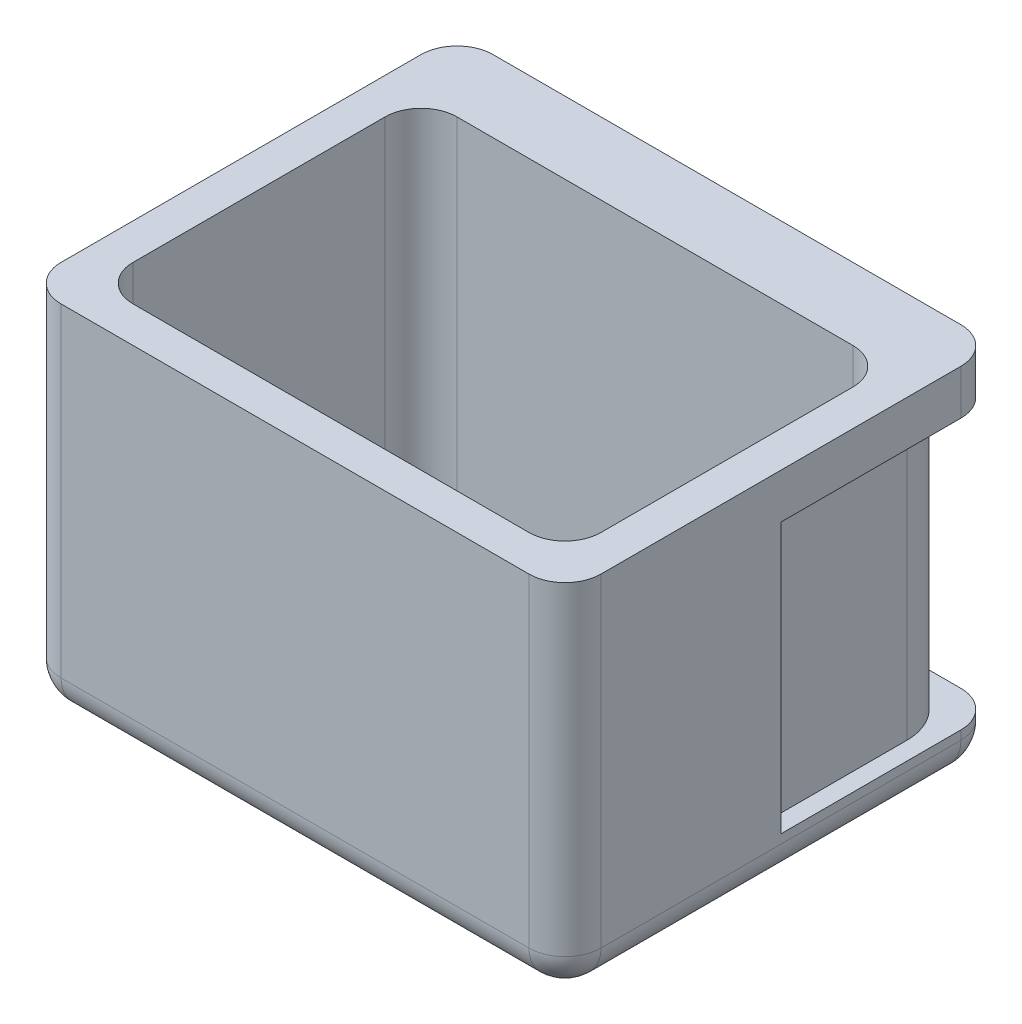
SolidWorks part; units mm, degrees
ref_plane "Front Plane" through (0, 0, 0) normal (0, 0, 1) x (1, 0, 0)
ref_plane "Top Plane" through (0, 0, 0) normal (0, 1, 0) x (1, 0, 0)
ref_plane "Right Plane" through (0, 0, 0) normal (1, 0, 0) x (0, 0, -1)
sketch "Sketch1" plane through (0, 0, 0) normal (0, 1, 0) x (1, 0, 0)
  line L1 (-75, -60) -> (75, -60)
  line L2 (-75, -60) -> (-75, 60)
  line L3 (-75, 60) -> (75, 60)
  line L4 (75, -60) -> (75, 60)
  line L5 (-75, -60) -> (75, 60) construction
  line L6 (-75, 60) -> (75, -60) construction
  point P0 (0, 0)
  dimension "D1" = 150
  dimension "D2" = 120
extrude "Boss-Extrude1" add sketch "Sketch1" along normal blind 100
fillet "Fillet1" radius 10 8 edges at (0, 0, -60) (-75, 0, 0) (0, 0, 60) (75, 0, 0) (-75, 50, -60) (75, 50, -60) (75, 50, 60) (-75, 50, 60)
shell "Shell1" thickness 10 removed face at (0, 100, 0)
fillet "Fillet2" radius 10 4 edges at (-65, 55, 50) (65, 55, 50) (65, 55, -50) (-65, 55, -50)
ref_plane "Plane1" through (0, 50, 0) normal (0, 1, 0) x (1, 0, 0)
sketch "Sketch2" plane through (0, 50, 0) normal (0, 1, 0) x (1, 0, 0)
  line L0 (-75, 0) -> (-65, 0)
  line L1 (-75, 50) -> (-75, -50) construction
  line L2 (75, -50) -> (75, 50) construction
  line L4 (65, 0) -> (75, 0)
  line L5 (70, 0) -> (70, 40)
  line L6 (55, 55) -> (-55, 55)
  line L7 (65, 60) -> (-65, 60)
  line L8 (-75, 50) -> (-75, -50)
  line L9 (-65, -60) -> (65, -60)
  line L10 (75, -50) -> (75, 50)
  line L11 (65, 60) -> (-65, 60)
  line L12 (-75, 50) -> (-75, 0)
  line L14 (75, 0) -> (75, 50)
  line L15 (-70, 40) -> (-70, 0)
  line L16 (55, 50) -> (-55, 50)
  line L17 (65, -40) -> (65, 40)
  line L18 (-55, -50) -> (55, -50)
  line L19 (-65, 40) -> (-65, -40)
  line L20 (55, 50) -> (-55, 50)
  line L21 (65, 0) -> (65, 40)
  line L23 (-65, 40) -> (-65, 0)
  arc A0 (70, 40) -> (55, 55) centre (55, 40) ccw
  arc A1 (-55, 55) -> (-70, 40) centre (-55, 40) ccw
  arc A4 (-65, 60) -> (-75, 50) centre (-65, 50) ccw
  arc A5 (-75, -50) -> (-65, -60) centre (-65, -50) ccw
  arc A6 (65, -60) -> (75, -50) centre (65, -50) ccw
  arc A7 (75, 50) -> (65, 60) centre (65, 50) ccw
  arc A8 (-65, 60) -> (-75, 50) centre (-65, 50) ccw
  arc A11 (75, 50) -> (65, 60) centre (65, 50) ccw
  arc A12 (65, 40) -> (55, 50) centre (55, 40) ccw
  arc A13 (55, -50) -> (65, -40) centre (55, -40) ccw
  arc A14 (-65, -40) -> (-55, -50) centre (-55, -40) ccw
  arc A15 (-55, 50) -> (-65, 40) centre (-55, 40) ccw
  arc A16 (65, 40) -> (55, 50) centre (55, 40) ccw
  arc A19 (-55, 50) -> (-65, 40) centre (-55, 40) ccw
  dimension "D1" = 0
  dimension "D2" = 0
  dimension "D3" = 5
extrude "Cut-Extrude1" cut sketch "Sketch2" against normal mid plane 75 contours L14 A11 L11 A8 L12 L0 L15 A1 L6 A0 L5 L4 region at (-73.3845, 50, -25)
sketch "Sketch4" plane through (0, 10, 0) normal (0, 1, 0) x (1, 0, 0)
  line L0 (-65, 40) -> (65, 40)
  line L1 (-55, 50) -> (55, 50) construction
  line L2 (-55, 50) -> (55, 50)
  arc A0 (65, 40) -> (55, 50) centre (55, 40) ccw construction
  arc A1 (-55, 50) -> (-65, 40) centre (-55, 40) ccw construction
  arc A2 (65, 40) -> (55, 50) centre (55, 40) ccw
  arc A3 (-55, 50) -> (-65, 40) centre (-55, 40) ccw
extrude "Boss-Extrude2" add sketch "Sketch4" along normal up to surface (90 mm away) up to face at (0, 100, 0)
sketch "Sketch3" plane through (0, 0, -55) normal (0, 0, -1) x (-1, 0, 0)
  line L0 (-55, 87.5) -> (55, 87.5) construction
  line L1 (-57.15, 87.5) -> (57.15, 87.5)
  line L2 (-57.15, 87.5) -> (-57.15, 36.7)
  line L3 (-57.15, 36.7) -> (57.15, 36.7)
  line L4 (57.15, 87.5) -> (57.15, 36.7)
  line L5 (-57.15, 87.5) -> (57.15, 36.7) construction
  line L6 (-57.15, 36.7) -> (57.15, 87.5) construction
  line L12 (-65, 100) -> (65, 100) construction
  point P0 (0, 62.1)
  point P11 (0, 100)
  dimension "D1" = 50.8
  dimension "D2" = 114.3
extrude "Cut-Extrude2" cut sketch "Sketch3" against normal mid plane 11
fillet "Fillet3" radius 10 2 edges at (65, 55, -40) (-65, 55, -40)
